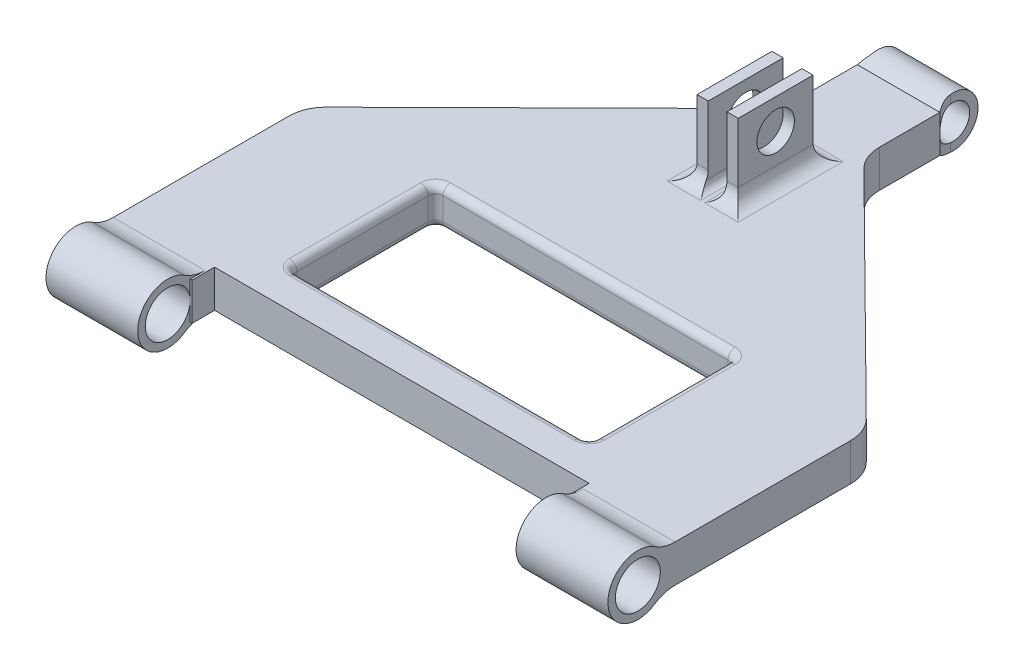
SolidWorks part; units mm, degrees
ref_plane "Front Plane" through (0, 0, 0) normal (0, 0, 1) x (1, 0, 0)
ref_plane "Top Plane" through (0, 0, 0) normal (0, 1, 0) x (1, 0, 0)
ref_plane "Right Plane" through (0, 0, 0) normal (1, 0, 0) x (0, 0, -1)
sketch "Sketch1" plane through (0, 0, 0) normal (0, 1, 0) x (1, 0, 0)
  line L3 (11.012, 112.2893) -> (75, 49)
  line L4 (75, 49) -> (75, -6)
  line L5 (75, -6) -> (50, -6)
  line L6 (50, -6) -> (50, 0)
  line L9 (-50, -6) -> (-75, -6)
  line L10 (-75, -6) -> (-75, 49)
  line L11 (-75, 49) -> (-11.012, 112.2893)
  line L12 (-50, 0) -> (-50, -6)
  line L16 (-50, 0) -> (50, 0)
  line L20 (-11.012, 112.2893) -> (11.012, 112.2893)
  line L21 (-11.012, 112.2893) -> (-11.012, 136.4569)
  line L22 (-11.012, 136.4569) -> (11.012, 136.4569)
  line L23 (11.012, 136.4569) -> (11.012, 112.2893)
  line L29 (40, 10) -> (-40, 10)
  line L30 (40, 10) -> (40, 49)
  line L31 (40, 49) -> (-40, 49)
  line L32 (-40, 10) -> (-40, 49)
  line L33 (40, 10) -> (-40, 49) construction
  line L34 (40, 49) -> (-40, 10) construction
  point P2 (0, 29.5)
  point P22 (0, 0)
  dimension "D10" = 10
  dimension "D13" = 22.024
  dimension "D1" = 90
  dimension "D2" = 90
  dimension "D3" = 55
  dimension "D4" = 55
  dimension "D5" = 100
  dimension "D6" = 25
  dimension "D7" = 25
  dimension "D8" = 6
  dimension "D9" = 6
  dimension "D11" = 10
  dimension "D12" = 10
  dimension "D14" = 80
extrude "Boss-Extrude1" add sketch "Sketch1" along normal blind 10
sketch "Sketch3" plane through (-75, 0, 0) normal (-1, 0, 0) x (0, 0, 1)
  line L0 (6, 5) -> (28.9479, 5) construction
  line L1 (6, 10) -> (6, 0) construction
  circle A0 centre (17.474, 5) radius 12.5161
  circle A1 centre (17.474, 5) radius 10
  dimension "D1" = 25.0321
  dimension "D2" = 20
ref_plane "Plane1" through (-62.5, 0, 0) normal (1, 0, 0) x (0, 0, -1)
sketch "Sketch4" plane through (-62.5, 0, 0) normal (1, 0, 0) x (0, 0, -1)
  line L0 (-6, 5) -> (-28.9479, 5) construction
  line L1 (-6, 10) -> (-6, 0) construction
  circle A0 centre (-12, 5) radius 8
  circle A1 centre (-12, 5) radius 6
  dimension "D1" = 16
  dimension "D2" = 12
extrude "Boss-Extrude2" add sketch "Sketch4" along normal blind 12 and the other way up to vertex (12.5 mm away) other way up to point (-75, 5, 6)
mirror "Mirror1" about plane through (0, 0, 0) normal (1, 0, 0) of "Boss-Extrude2"
sketch "Sketch10" plane through (0, 10, 0) normal (0, 1, 0) x (1, 0, 0)
  line L1 (11.012, 132.5806) -> (-11.012, 132.5806)
  line L2 (11.012, 132.5806) -> (11.012, 112.2893)
  line L3 (11.012, 112.2893) -> (-11.012, 112.2893)
  line L4 (-11.012, 132.5806) -> (-11.012, 112.2893)
  line L5 (11.012, 132.5806) -> (-11.012, 112.2893) construction
  line L6 (11.012, 112.2893) -> (-11.012, 132.5806) construction
  point P0 (0, 122.4349)
extrude "Boss-Extrude4" add sketch "Sketch10" against normal up to surface (10 mm away) up to face at (0, 0, -29.5)
sketch "Sketch12" plane through (0, 0, 0) normal (1, 0, 0) x (0, 0, -1)
  line L0 (117.2933, 6.865) -> (137.0894, 6.865)
  arc A0 (129.5699, 6.865) -> (117.2933, 6.865) centre (123.4316, 6.865) ccw
sketch "Sketch11" plane through (0, 10, 0) normal (0, 1, 0) x (1, 0, 0)
  circle A0 centre (0, 123.4316) radius 5
  dimension "D1" = 10
sketch "Sketch13" plane through (0, 10, 0) normal (0, 1, 0) x (1, 0, 0)
  line L0 (0, 125.8475) -> (0, 49) construction
  line L1 (40, 49) -> (-40, 49) construction
  line L3 (-5.5, 104.2893) -> (-2.5, 104.2893)
  line L4 (-5.5, 104.2893) -> (-5.5, 84.2893)
  line L5 (-5.5, 84.2893) -> (-2.5, 84.2893)
  line L6 (-2.5, 104.2893) -> (-2.5, 84.2893)
  line L7 (-5.5, 104.2893) -> (-2.5, 84.2893) construction
  line L8 (-5.5, 84.2893) -> (-2.5, 104.2893) construction
  line L9 (2.5, 104.2893) -> (5.5, 104.2893)
  line L10 (2.5, 104.2893) -> (2.5, 84.2893)
  line L11 (2.5, 84.2893) -> (5.5, 84.2893)
  line L12 (5.5, 104.2893) -> (5.5, 84.2893)
  line L13 (2.5, 104.2893) -> (5.5, 84.2893) construction
  line L14 (2.5, 84.2893) -> (5.5, 104.2893) construction
  point P4 (-4, 94.2893)
  point P9 (4, 94.2893)
  dimension "D1" = 20
  dimension "D2" = 20
  dimension "D3" = 2.5
  dimension "D4" = 2.5
  dimension "D5" = 3
  dimension "D6" = 3
  dimension "D7" = 8
  dimension "D8" = 8
extrude "Boss-Extrude5" add sketch "Sketch13" along normal blind 20
sketch "Sketch14" plane through (5.5, 0, 0) normal (1, 0, 0) x (0, 0, -1)
  line L5 (84.2893, 30) -> (84.2893, 10) construction
  line L6 (84.2893, 30) -> (104.2893, 30) construction
  circle A0 centre (94.2893, 22) radius 5
  point P2 (94.3976, 21.9724)
  point P7 (87.3168, 17.2852)
  dimension "D1" = 10
  dimension "D2" = 10
  dimension "D3" = 8
extrude "Cut-Extrude1" cut sketch "Sketch14" against normal blind 15
sketch "Sketch15" plane through (11.012, 0, 0) normal (1, 0, 0) x (0, 0, -1)
  line L0 (132.5806, 5) -> (162.7146, 5)
  line L1 (132.5806, 0) -> (132.5806, 10) construction
  circle A0 centre (137.0806, 5) radius 4.5
  circle A1 centre (137.0806, 5) radius 6.7268
  point P7 (132.5806, 5)
  dimension "D1" = 9
  dimension "D2" = 13.4536
sketch "Sketch16" plane through (0, 0, 0) normal (1, 0, 0) x (0, 0, -1)
  line L0 (132.5806, 5) -> (156.2383, 5)
  circle A0 centre (137.0806, 5) radius 4.5
  circle A1 centre (137.0806, 5) radius 6.7268
  dimension "D1" = 9
  dimension "D2" = 13.4536
extrude "Boss-Extrude6" add sketch "Sketch16" along normal blind 10 and the other way blind 10
fillet "Fillet2" radius 4 3 edges at (-4, 10, -84.2893) (-4, 10, -104.2893) (-5.5, 10, -94.2893)
fillet "Fillet4" radius 2 12 edges at (-40, 10, -29.5) (0, 0, -10) (40, 10, -29.5) (-40, 5, -10) (0, 10, -10) (40, 5, -10) (40, 0, -29.5) (0, 0, -49) (40, 5, -49) (0, 10, -49) (-40, 5, -49) (-40, 0, -29.5)
fillet "Fillet8" radius 10 8 edges at (-11.012, 5, -112.2893) (11.012, 5, -112.2893) (-75, 5, -49) (-62.75, 10, 5.755) (-62.75, 0, 5.755) (62.75, 0, 5.755) (62.75, 10, 5.755) (75, 5, -49)
fillet "Fillet9" radius 8 4 edges at (-10, 2.5, -132.5806) (-10, 7.5, -132.5806) (10, 7.5, -132.5806) (10, 2.5, -132.5806)
ref_plane "Plane2" through (4, 0, 0) normal (1, 0, 0) x (0, 0, -1)
ref_plane "Plane3" through (-4, 0, 0) normal (1, 0, 0) x (0, 0, -1)
sketch "Sketch19" plane through (4, 0, 0) normal (1, 0, 0) x (0, 0, -1)
  line L0 (84.2893, 30) -> (66.3018, 10)
  line L1 (125.8475, 10) -> (49, 10) construction
fillet "Fillet15" radius 4 3 edges at (4, 10, -84.2893) (5.5, 10, -94.2893) (4, 10, -104.2893)
fillet "Fillet16" radius 2 2 edges at (-2.5, 10, -94.2893) (2.5, 10, -94.2893)
